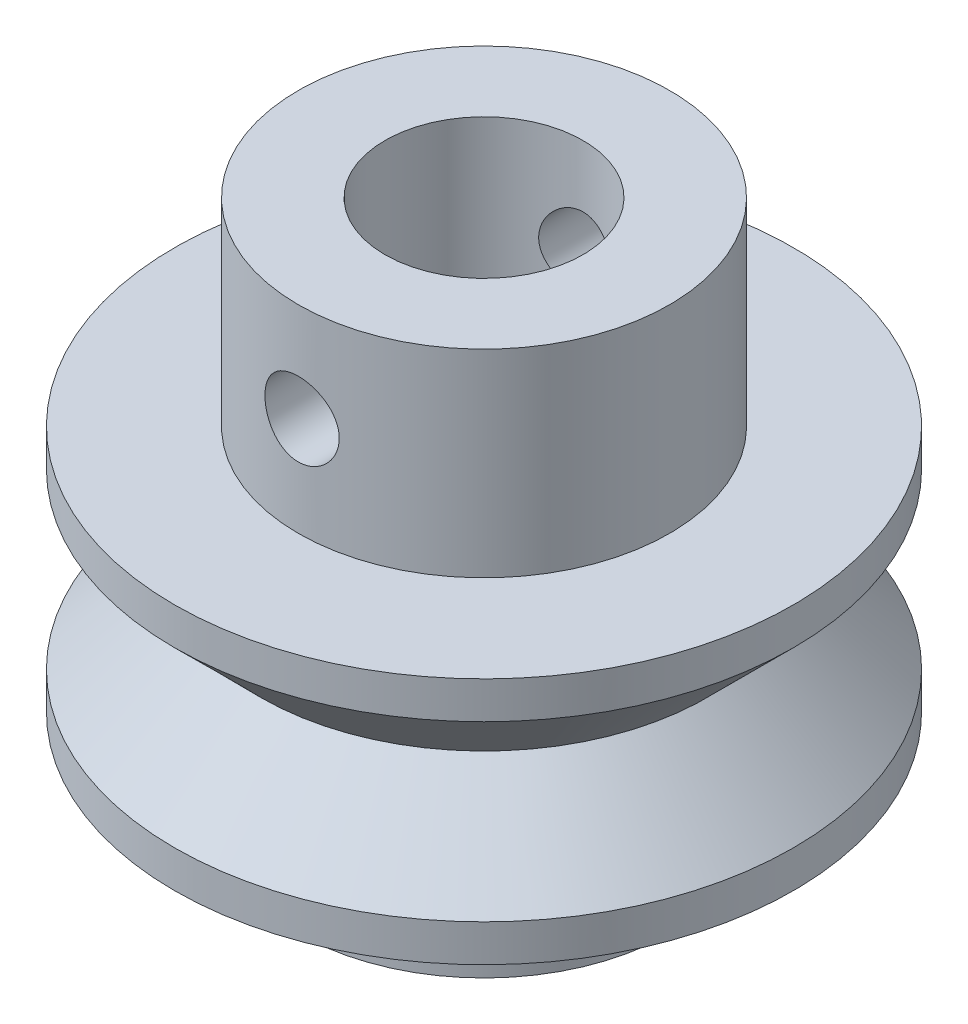
SolidWorks part; units mm, degrees
ref_plane "Front Plane" through (0, 0, 0) normal (0, 0, 1) x (1, 0, 0)
ref_plane "Top Plane" through (0, 0, 0) normal (0, 1, 0) x (1, 0, 0)
ref_plane "Right Plane" through (0, 0, 0) normal (1, 0, 0) x (0, 0, -1)
sketch "Sketch1" plane through (0, 0, 0) normal (0, 1, 0) x (1, 0, 0)
  circle A0 centre (0, 0) radius 4
  circle A1 centre (0, 0) radius 7.5
  circle A2 centre (0, 0) radius 12.5
  dimension "D1" = 8
  dimension "D2" = 15
  dimension "D3" = 25
extrude "Boss-Extrude1" add sketch "Sketch1" against normal blind 9 and the other way blind 13 contours A1 A0 region at (-7.2879, 0, 0)
extrude "Boss-Extrude2" add sketch "Sketch1<4>" along normal blind 5 and the other way blind 5 contours A2 A1 region at (-12.1464, 0, 0)
sketch "Sketch1<4>" plane through (0, 0, 0) normal (0, 1, 0) x (1, 0, 0) same geometry as "Sketch1"
sketch "Sketch2" plane through (0, 0, 0) normal (1, 0, 0) x (0, 0, -1)
  line L0 (-12.5, 5) -> (-12.5, 3.5)
  line L1 (-12.5, 5) -> (-12.5, -5) construction
  line L2 (-12.5, 3.5) -> (-9, 0)
  line L3 (-9, 0) -> (-12.5, -3.5)
  line L4 (-12.5, -5) -> (-12.5, -3.5)
  line L5 (-9, 0) -> (-12.5, 0) construction
  line L6 (-12.5, 3.5) -> (-12.5, -3.5)
  line L7 (0, 0) -> (0, 3.3647) construction
  dimension "D1" = 1.5
  dimension "D2" = 1.5
  dimension "D3" = 9
revolve "Cut-Revolve1" cut sketch "Sketch2" angle 360 about L7 region at (0, 0, 11.3333)
sketch "Sketch3" plane through (0, 0, 0) normal (0, 0, 1) x (1, 0, 0)
  line L0 (0, 5) -> (0, 9) construction
  line L1 (12.5, 5) -> (-12.5, 5) construction
  circle A0 centre (0, 9) radius 1.5
  dimension "D1" = 3
extrude "Cut-Extrude1" cut sketch "Sketch3" against normal through all both and the other way through all contours A0 region at (0, 9, 0)
